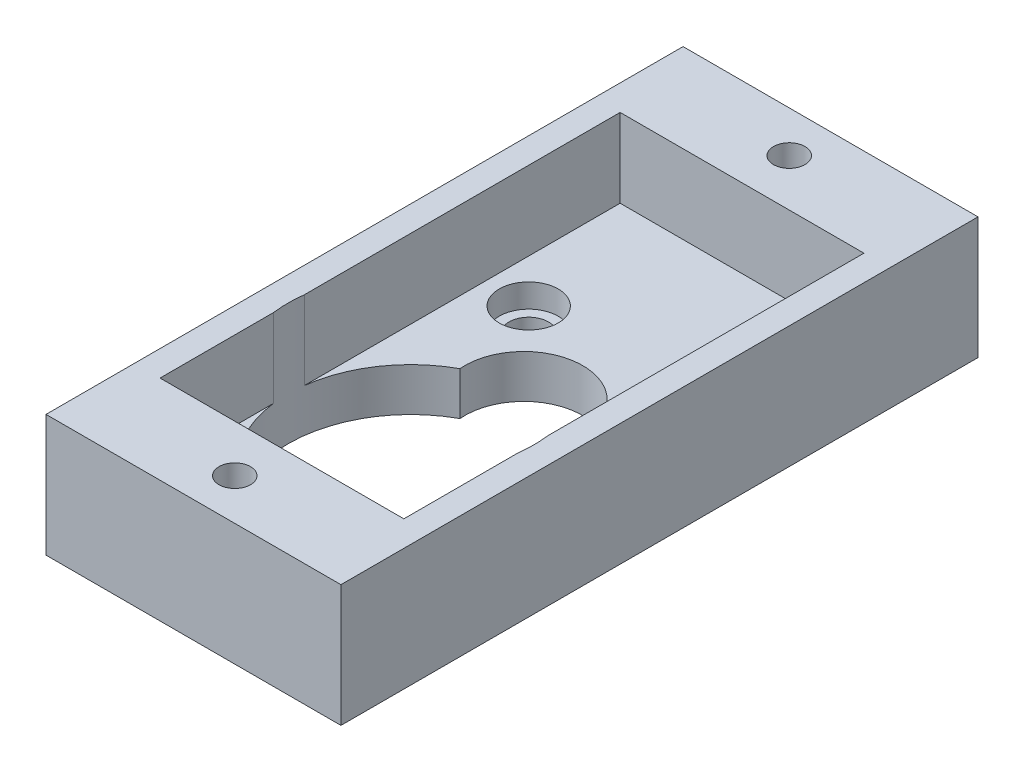
SolidWorks part; units mm, degrees
note: The reader was unsure of these and kept them because the rebuilt part matched: shared geometry of "草图1<3>", "草图4<3>".
ref_plane "前视基准面" through (0, 0, 0) normal (0, 0, 1) x (1, 0, 0)
ref_plane "上视基准面" through (0, 0, 0) normal (0, 1, 0) x (1, 0, 0)
ref_plane "右视基准面" through (0, 0, 0) normal (1, 0, 0) x (0, 0, -1)
other "Configuration Table"
sketch "草图1" plane through (0, 0, 0) normal (0, 1, 0) x (1, 0, 0)
  line L1 (0, 0) -> (15, 0)
  line L2 (0, 0) -> (0, -32.4)
  line L3 (0, -32.4) -> (15, -32.4)
  line L4 (15, 0) -> (15, -32.4)
  circle A4 centre (3, -3) radius 0.8
  circle A5 centre (12, -3) radius 0.8
  circle A6 centre (3, -29.4) radius 0.8
  circle A7 centre (12, -29.4) radius 0.8
  circle A8 centre (7.5, -21.35) radius 6.25
  circle A9 centre (7.5, -15.6) radius 3
  point P10 (7.5, -32.4)
  dimension "D3" = 1.6
  dimension "D6" = 12.5
  dimension "D7" = 6
  dimension "D1" = 3
  dimension "D2" = 15
  dimension "D4" = 11.05
  dimension "D5" = 5.75
  dimension "D9" = 3
  dimension "D10" = 3
  dimension "D11" = 3
  dimension "32.4" = 32.4
extrude "凸台-拉伸1" add sketch "草图1" along normal blind 2.2
extrude "切除-拉伸1" cut sketch "草图1<3>" along normal through all contours A9 | A8
sketch "草图1<3>" plane through (0, 0, 0) normal (0, 1, 0) x (1, 0, 0) same geometry as "草图1"
sketch "草图2" plane through (0, 2.2, 0) normal (0, 1, 0) x (1, 0, 0)
  line L0 (0, 0) -> (0, -32.4) construction
  line L1 (15, -32.4) -> (0, -32.4)
  line L2 (15, -32.4) -> (15, -27.9)
  line L3 (15, -27.9) -> (0, -27.9)
  line L4 (0, -32.4) -> (0, -27.9)
  line L6 (15, 0) -> (0, 0)
  line L7 (15, 0) -> (15, -4.5)
  line L8 (15, -4.5) -> (0, -4.5)
  line L9 (0, 0) -> (0, -4.5)
  line L10 (15, -32.4) -> (13.7, -32.4)
  line L11 (15, -32.4) -> (15, 0)
  line L12 (15, 0) -> (13.7, 0)
  line L13 (13.7, -32.4) -> (13.7, 0)
  line L15 (0, 0) -> (1.3, 0)
  line L16 (0, 0) -> (0, -32.4)
  line L17 (0, -32.4) -> (1.3, -32.4)
  line L18 (1.3, 0) -> (1.3, -32.4)
  dimension "D1" = 4.5
  dimension "D2" = 1.3
  dimension "D3" = 1.3
extrude "凸台-拉伸2" add sketch "草图2" along normal blind 4
sketch "草图3" plane through (0, 6.2, 0) normal (0, 1, 0) x (1, 0, 0)
  line L1 (15, 0) -> (0, 0) construction
  line L2 (0, -32.4) -> (15, -32.4) construction
  circle A0 centre (7.5, -30.3) radius 0.8
  circle A1 centre (7.5, -2.1) radius 0.8
  point P11 (7.5, -32.4)
  dimension "D1" = 1.6
  dimension "D2" = 2.1
  dimension "D3" = 2.1
extrude "切除-拉伸2" cut sketch "草图3" against normal blind 3 contours A1 | A0
sketch "草图4" plane through (0, 2.2, 0) normal (0, 1, 0) x (1, 0, 0)
  line L0 (11.5, -11.35) -> (3.5, -11.35) construction
  line L1 (7.5, -11.35) -> (7.5, -21.35) construction
  circle A0 centre (11.5, -11.35) radius 1.5
  circle A1 centre (3.5, -11.35) radius 1.5
  arc A2 (1.3, -22.139) -> (13.7, -22.139) centre (7.5, -21.35) ccw construction
  circle A3 centre (11.5, -11.35) radius 1
  circle A4 centre (3.5, -11.35) radius 1
  dimension "D3" = 3
  dimension "D4" = 2
  dimension "D1" = 8
  dimension "D2" = 10
extrude "切除-拉伸3" cut sketch "草图4" against normal through all contours A4 | A3
extrude "切除-拉伸4" cut sketch "草图4<3>" against normal blind 1.2
sketch "草图4<3>" plane through (0, 2.2, 0) normal (0, 1, 0) x (1, 0, 0) same geometry as "草图4"
